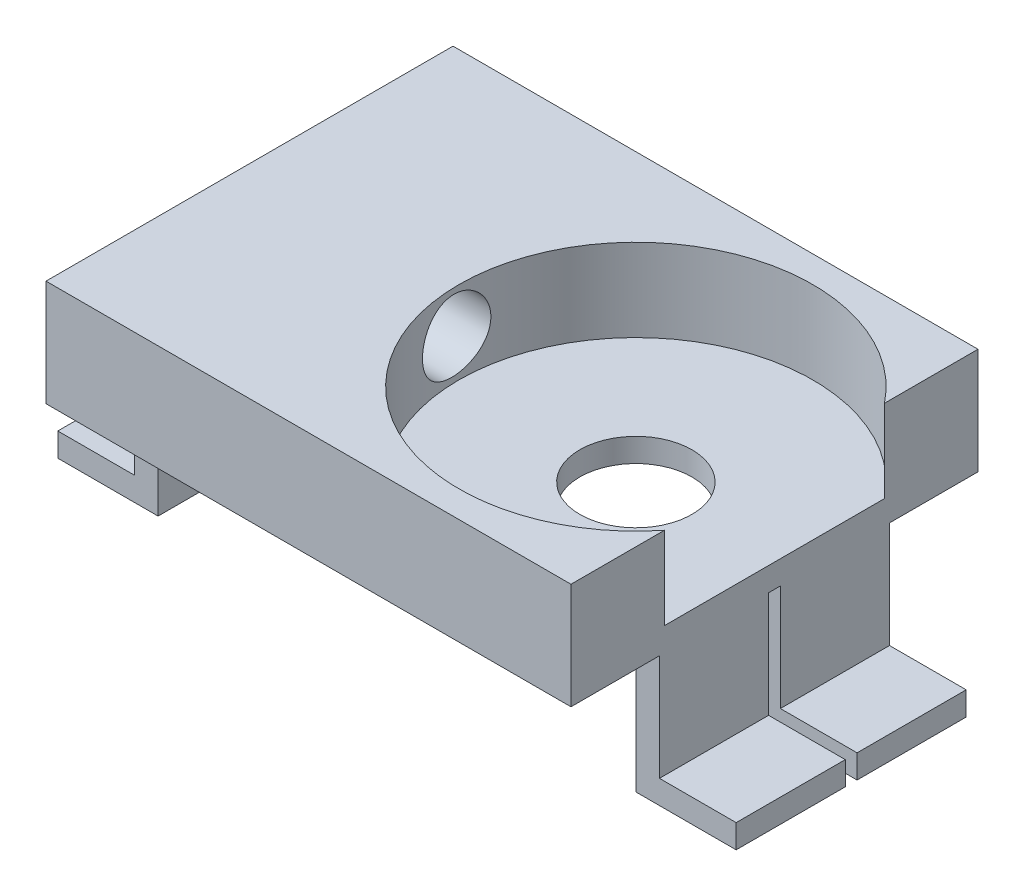
SolidWorks part; units mm, degrees
ref_plane "Front Plane" through (0, 0, 0) normal (0, 0, 1) x (1, 0, 0)
ref_plane "Top Plane" through (0, 0, 0) normal (0, 1, 0) x (1, 0, 0)
ref_plane "Right Plane" through (0, 0, 0) normal (1, 0, 0) x (0, 0, -1)
sketch "Sketch1" plane through (0, 0, 0) normal (0, 0, 1) x (1, 0, 0)
  line L0 (-9.0568, 11) -> (31.4432, 11)
  line L1 (31.4432, 11) -> (31.4432, 0)
  line L2 (31.4432, 0) -> (39.9432, 0)
  line L3 (39.9432, 0) -> (39.9432, 2)
  line L4 (39.9432, 2) -> (33.4432, 2)
  line L5 (33.4432, 2) -> (33.4432, 20)
  line L6 (33.4432, 20) -> (-11.0568, 20)
  line L7 (-11.0568, 20) -> (-11.0568, 2)
  line L8 (-11.0568, 2) -> (-17.5568, 2)
  line L9 (-17.5568, 2) -> (-17.5568, 0)
  line L10 (-17.5568, 0) -> (-9.0568, 0)
  line L11 (-9.0568, 0) -> (-9.0568, 11)
  dimension "D1" = 11
  dimension "D2" = 40.5
  dimension "D3" = 2
  dimension "D4" = 2
  dimension "D5" = 9
  dimension "D6" = 2
  dimension "D7" = 2
  dimension "D8" = 6.5
  dimension "D9" = 6.5
extrude "Boss-Extrude1" add sketch "Sketch1" along normal blind 34.5
sketch "Sketch3" plane through (0, 20, 0) normal (0, 1, 0) x (1, 0, 0)
  line L1 (33.4432, 0) -> (-11.0568, 0) construction
  line L2 (31.4432, -34.5) -> (31.4432, 0) construction
  circle A0 centre (21.6932, -17.25) radius 15
  dimension "D1" = 30
  dimension "D2" = 9.75
  dimension "D3" = 17.25
extrude "Cut-Extrude1" cut sketch "Sketch3" against normal blind 7
sketch "Sketch4" plane through (-17.5568, 0, 0) normal (-1, 0, 0) x (0, 0, 1)
  line L1 (0, 0) -> (7.5, 0)
  line L2 (0, 0) -> (0, 11)
  line L3 (0, 11) -> (7.5, 11)
  line L4 (7.5, 0) -> (7.5, 11)
  line L5 (34.5, 0) -> (27, 0)
  line L6 (34.5, 0) -> (34.5, 11)
  line L7 (34.5, 11) -> (27, 11)
  line L8 (27, 0) -> (27, 11)
  dimension "D1" = 7.5
  dimension "D2" = 7.5
  dimension "D3" = 11
  dimension "D4" = 11
extrude "Cut-Extrude2" cut sketch "Sketch4" against normal through all
sketch "Sketch5" plane through (0, 13, 0) normal (0, 1, 0) x (1, 0, 0)
  circle A0 centre (21.6932, -17.25) radius 4.75
  dimension "D1" = 9.5
extrude "Cut-Extrude3" cut sketch "Sketch5" against normal through all
sketch "Sketch6" plane through (39.9432, 0, 0) normal (1, 0, 0) x (0, 0, -1)
  line L0 (-27, 0) -> (-7.5, 0) construction
  line L1 (-17.75, 0) -> (-16.75, 0)
  line L2 (-17.75, 0) -> (-17.75, 11)
  line L3 (-17.75, 11) -> (-16.75, 11)
  line L4 (-16.75, 0) -> (-16.75, 11)
  line L5 (-7.5, 11) -> (0, 11) construction
  line L6 (-7.5, 2) -> (-7.5, 11) construction
  dimension "D1" = 1
  dimension "D2" = 0
  dimension "D3" = 9.25
extrude "Cut-Extrude4" cut sketch "Sketch6" against normal through all
sketch "Sketch7" plane through (-11.0568, 0, 0) normal (-1, 0, 0) x (0, 0, 1)
  line L0 (27, 2) -> (27, 11) construction
  line L1 (34.5, 20) -> (0, 20) construction
  circle A0 centre (17.75, 16.5) radius 3
  dimension "D1" = 6
  dimension "D2" = 9.25
  dimension "D3" = 3.5
extrude "Cut-Extrude5" cut sketch "Sketch7" against normal up to next
